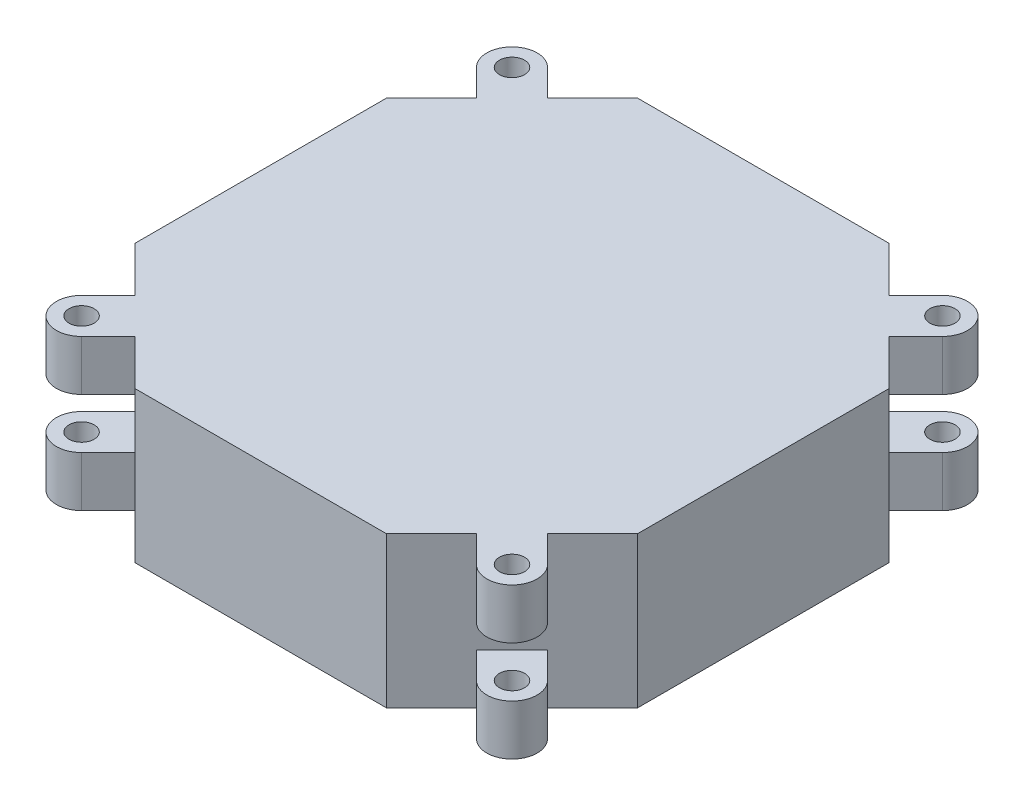
SolidWorks part; units mm, degrees
ref_plane "Front Plane" through (0, 0, 0) normal (0, 0, 1) x (1, 0, 0)
ref_plane "Top Plane" through (0, 0, 0) normal (0, 1, 0) x (1, 0, 0)
ref_plane "Right Plane" through (0, 0, 0) normal (1, 0, 0) x (0, 0, -1)
ref_axis "X" through (-88.99, 0, 0) along (1, 0, 0)
ref_axis "Y" through (0, 55, 0) along (0, -1, 0)
ref_axis "Z" through (0, 0, -88.99) along (0, 0, 1)
sketch "Sketch1" plane through (0, 0, 0) normal (0, 1, 0) x (1, 0, 0)
  line L0 (50, -100) -> (100, -50)
  line L1 (-100, 100) -> (100, 100)
  line L2 (-100, 100) -> (-100, -100)
  line L3 (-100, -100) -> (100, -100)
  line L4 (100, 100) -> (100, -100)
  line L5 (-100, 100) -> (100, -100) construction
  line L6 (-100, -100) -> (100, 100) construction
  line L7 (100, 50) -> (50, 100)
  line L8 (-50, 100) -> (-100, 50)
  line L11 (-100, -50) -> (-50, -100)
  point P0 (0, 0)
  dimension "D1" = 200
  dimension "D2" = 200
  dimension "D3" = 45
  dimension "D4" = 50
extrude "Boss-Extrude1" add sketch "Sketch1" along normal blind 60 contours L2 L11 L3 L0 L4 L7 L1 L8 region at (0, 0, 0)
sketch "Sketch2" plane through (0, 0, 0) normal (0, 1, 0) x (1, 0, 0)
  line L0 (50, -100) -> (100, -50) construction
  line L1 (50, -100) -> (100, -50)
  line L2 (67.9289, -82.0711) -> (78.5355, -92.6777)
  line L3 (92.6777, -78.5355) -> (82.0711, -67.9289)
  line L4 (85.6066, -85.6066) -> (75, -75) construction
  arc A0 (78.5355, -92.6777) -> (92.6777, -78.5355) centre (85.6066, -85.6066) ccw
  circle A1 centre (85.6066, -85.6066) radius 5
  point P8 (98.187, -77.4376)
  dimension "D1" = 5
  dimension "D2" = 10
  dimension "D3" = 15
extrude "Boss-Extrude2" add sketch "Sketch2" along normal blind 20 contours A1 L1 L2 A0 L3 region at (75.2768, 0, 75.2768)
extrude "Boss-Extrude3" add sketch "Sketch2<3>" against normal offset from surface (20 mm away) 20 from surface contours A1 L1 L2 A0 L3 region at (75.2768, 0, 75.2768) up to face at (82.0711, 20, 82.0711) starting at face at (0, 60, 0)
sketch "Sketch2<3>" plane through (0, 0, 0) normal (0, 1, 0) x (1, 0, 0) same geometry as "Sketch2"
pattern_circular "CirPattern1" count 4 every 90 about axis through (0, 55, 0) along (0, -1, 0) of "Boss-Extrude3", "Boss-Extrude2"
